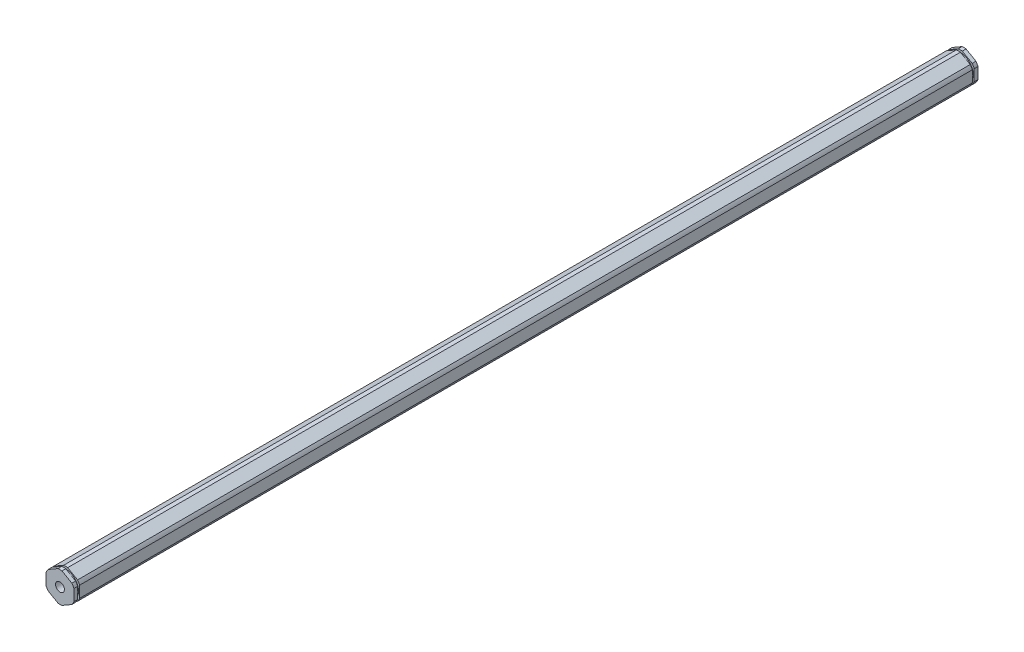
SolidWorks part; units mm, degrees
ref_plane "Front Plane" through (0, 0, 0) normal (0, 0, 1) x (1, 0, 0)
ref_plane "Top Plane" through (0, 0, 0) normal (0, 1, 0) x (1, 0, 0)
ref_plane "Right Plane" through (0, 0, 0) normal (1, 0, 0) x (0, 0, -1)
sketch "Sketch1" plane through (0, 0, 0) normal (0, 0, 1) x (1, 0, 0)
  line L1 (0, 7.3323) -> (-6.35, 3.6662)
  line L2 (-6.35, 3.6662) -> (-6.35, -3.6662)
  line L3 (-6.35, -3.6662) -> (0, -7.3323)
  line L4 (0, -7.3323) -> (6.35, -3.6662)
  line L5 (6.35, -3.6662) -> (6.35, 3.6662)
  line L6 (6.35, 3.6662) -> (0, 7.3323)
  circle A0 centre (0, 0) radius 6.35 construction
  circle A1 centre (0, 0) radius 6.858
  dimension "D1" = 12.7
  dimension "D2" = 13.716
extrude "Boss-Extrude1" add sketch "Sketch1" along normal mid plane 411.4927 contours L5 A1 L6 L1 L2 L3 L4 region at (0, 0, 0)
hole_wizard "#10-32 Tapped Hole1" positions "3DSketch1" profile "Sketch2" tap size "#10-32" standard "ANSI Inch"
sketch3d "3DSketch1"
  line L0 (0, 0, 205.7464) -> (0, 0, -205.7464) construction
  line L1 (0, 0, 205.7464) -> (0, 0, -205.7464) construction
  point P0 (0, 0, 205.7464)
  point P4 (0, 0, -205.7464)
sketch "Sketch2" plane through (0, 0, 205.7464) normal (1, 0, 0) x (0, -1, 0)
  line L0 (0, 0) -> (0, 17.5608)
  line L1 (0, 17.5608) -> (2.0193, 16.3474)
  line L2 (2.0193, 16.3474) -> (2.0193, 0)
  line L5 (2.0193, 0) -> (0, 0)
  line L10 (0, 17.5608) -> (-2.0193, 16.3474) construction
  line L11 (0, -6.35) -> (0, 107.95) construction
  dimension "Tap Drill Dia." = 4.0386
  dimension "Tap Drill Depth" = 16.3474
  dimension "Drill Angle" = 118
cosmetic thread "Hole Thread1" parameters "D1"=13.97, "D2"=4.826
cosmetic thread "Hole Thread2" parameters "D1"=13.97, "D2"=4.826
sketch "Sketch5" plane through (0, 0, 0) normal (1, 0, 0) x (0, 0, -1)
  line L0 (205.7464, 6.858) -> (-205.7464, 6.858) construction
  line L1 (-204.0319, 6.858) -> (-203.1429, 6.858)
  line L2 (-204.0319, 6.858) -> (-204.0319, 5.8547)
  line L3 (-204.0319, 5.8547) -> (-203.1429, 5.8547)
  line L4 (-203.1429, 6.858) -> (-203.1429, 5.8547)
  line L5 (-165.0472, 0) -> (-158.8423, 0) construction
  dimension "D1" = 5.8547
  dimension "D2" = 0.889
  dimension "D3" = 1.7145
revolve "Cut-Revolve1" cut sketch "Sketch5" angle 360 about L5
mirror "Mirror1" about plane through (0, 0, 0) normal (0, 0, 1) of "Cut-Revolve1"
